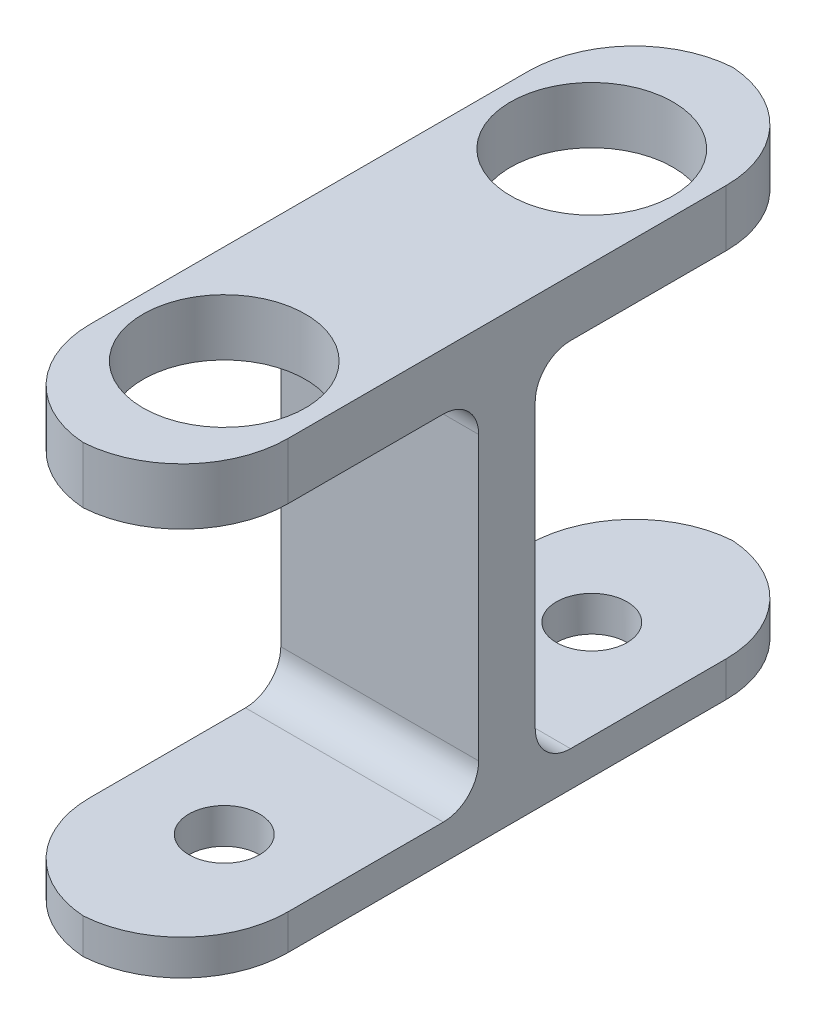
SolidWorks part; units mm, degrees
ref_plane "Front Plane" through (0, 0, 0) normal (0, 0, 1) x (1, 0, 0)
ref_plane "Top Plane" through (0, 0, 0) normal (0, 1, 0) x (1, 0, 0)
ref_plane "Right Plane" through (0, 0, 0) normal (1, 0, 0) x (0, 0, -1)
sketch "Sketch1" plane through (0, 0, 0) normal (1, 0, 0) x (0, 0, -1)
  line L0 (0, 0) -> (42, 0)
  line L1 (42, 0) -> (42, -50)
  line L2 (42, -50) -> (0, -50)
  line L3 (0, -50) -> (0, -55)
  line L4 (0, -55) -> (46, -55)
  line L5 (46, -55) -> (46, 8)
  line L6 (46, 8) -> (0, 8)
  line L7 (0, 8) -> (0, 0)
  dimension "D1" = 42
  dimension "D2" = 50
  dimension "D3" = 8
  dimension "D4" = 4
  dimension "D5" = 5
extrude "Boss-Extrude1" add sketch "Sketch1" along normal blind 28 contours L0 L1 L2 L3 L4 L5 L6 L7
sketch "Sketch2" plane through (0, 8, 0) normal (0, 1, 0) x (1, 0, 0)
  line L0 (28, 0) -> (0, 0) construction
  circle A0 centre (14, 20) radius 11.5
  point P2 (14, 0)
  dimension "D1" = 23
  dimension "D2" = 20
extrude "Cut-Extrude1" cut sketch "Sketch2" against normal up to next
sketch "Sketch3" plane through (0, -50, 0) normal (0, 1, 0) x (1, 0, 0)
  circle A0 centre (14, 20) radius 5
  circle A1 centre (14, 20) radius 11.5 construction
  dimension "D1" = 10
extrude "Cut-Extrude2" cut sketch "Sketch3" against normal up to next contours A0
fillet "Fillet2" radius 5 2 edges at (14, 0, -42) (14, -50, -42)
mirror "Mirror2" about plane through (28, -55, -46) normal (0, 0, 1) of "Fillet2", "Boss-Extrude1", "Cut-Extrude1", "Cut-Extrude2"
fillet "Fillet3" radius 15 8 edges at (28, -52.5, 0) (0, -52.5, 0) (28, 4, 0) (0, 4, 0) (0, 4, -92) (0, -52.5, -92) (28, -52.5, -92) (28, 4, -92)
